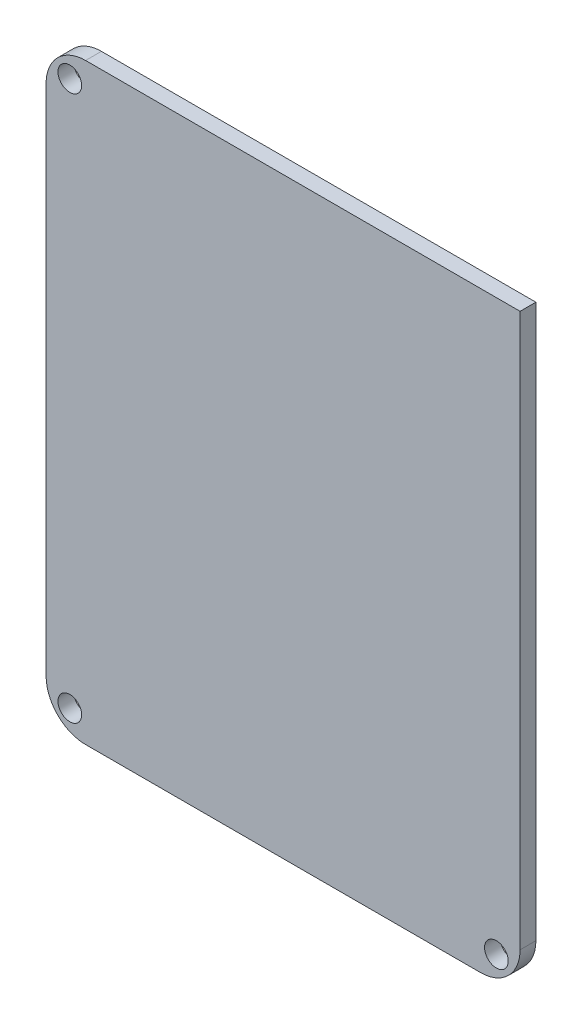
SolidWorks part; units mm, degrees
ref_plane "Front Plane" through (0, 0, 0) normal (0, 0, 1) x (1, 0, 0)
ref_plane "Top Plane" through (0, 0, 0) normal (0, 1, 0) x (1, 0, 0)
ref_plane "Right Plane" through (0, 0, 0) normal (1, 0, 0) x (0, 0, -1)
sketch "Sketch1" plane through (0, 0, 0) normal (0, 0, 1) x (1, 0, 0)
  line L1 (-53.9067, 69.7985) -> (6.0933, 69.7985)
  line L2 (-53.9067, 69.7985) -> (-53.9067, -5.2015)
  line L3 (-53.9067, -5.2015) -> (6.0933, -5.2015)
  line L4 (6.0933, 69.7985) -> (6.0933, -5.2015)
extrude "Boss-Extrude1" add sketch "Sketch1" along normal blind 2
sketch "Sketch2" plane through (0, 0, 2) normal (0, 0, 1) x (1, 0, 0)
  line L1 (-53.9067, -5.2015) -> (-50.9067, -5.2015)
  line L2 (-53.9067, -5.2015) -> (-53.9067, -2.2015)
  line L3 (-53.9067, -2.2015) -> (-50.9067, -2.2015)
  line L4 (-50.9067, -5.2015) -> (-50.9067, -2.2015)
  line L5 (6.0933, -5.2015) -> (3.0933, -5.2015)
  line L6 (6.0933, -5.2015) -> (6.0933, -2.2015)
  line L7 (6.0933, -2.2015) -> (3.0933, -2.2015)
  line L8 (3.0933, -5.2015) -> (3.0933, -2.2015)
  line L9 (-53.9067, 69.7985) -> (-50.9067, 69.7985)
  line L10 (-53.9067, 69.7985) -> (-53.9067, 66.7985)
  line L11 (-53.9067, 66.7985) -> (-50.9067, 66.7985)
  line L12 (-50.9067, 69.7985) -> (-50.9067, 66.7985)
  circle A0 centre (-50.9067, 66.7985) radius 1.5
  circle A1 centre (-50.9067, -2.2015) radius 1.5
  circle A2 centre (3.0933, -2.2015) radius 1.5
extrude "Cut-Extrude1" cut sketch "Sketch2" against normal blind 2 contours L12 A0 L11 | L11 A0 L12 | L7 A2 L8 | L8 A2 L7 | L3 A1 L4 | L4 A1 L3 region at (-51.5434, -2.8381, 2) region at (-50.6945, -1.9893, 2) region at (2.8811, -1.9893, 2) region at (3.7299, -2.8381, 2) region at (-50.6945, 66.5863, 2) region at (-51.5434, 67.4351, 2)
fillet "Fillet1" radius 5 3 edges at (6.0933, -5.2015, 1) (-53.9067, -5.2015, 1) (-53.9067, 69.7985, 1) first distance on face at (-23.9067, -5.2015, 1) first distance on face at (-23.9067, 69.7985, 1)
